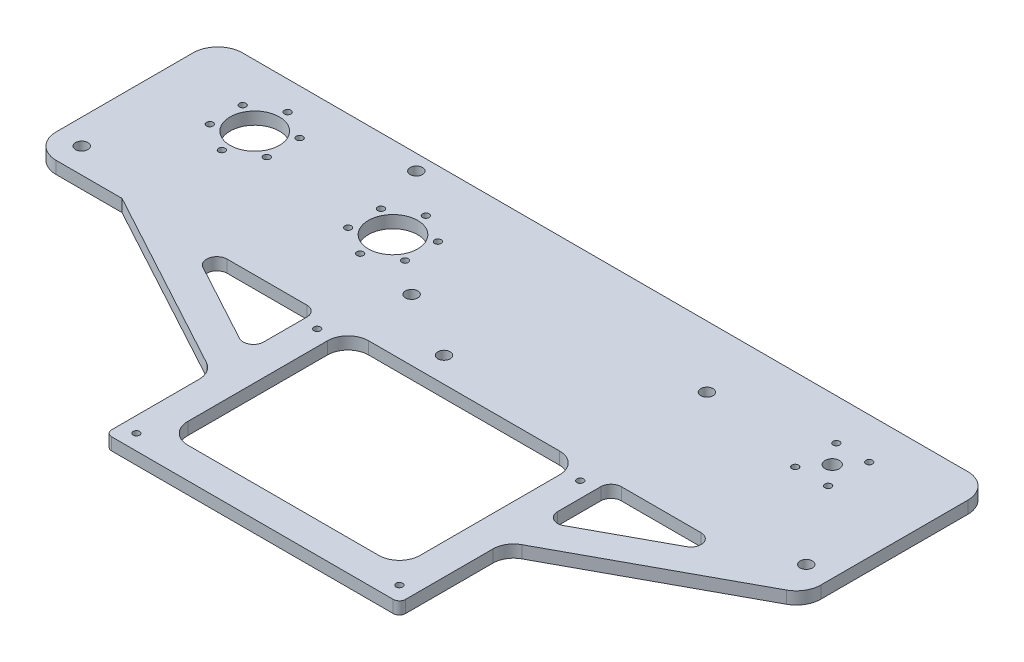
SolidWorks part; units mm, degrees
ref_plane "Plano frontal" through (0, 0, 0) normal (0, 0, 1) x (1, 0, 0)
ref_plane "Plano superior" through (0, 0, 0) normal (0, 1, 0) x (1, 0, 0)
ref_plane "Plano direito" through (0, 0, 0) normal (1, 0, 0) x (0, 0, -1)
sketch "Esboço1" plane through (0, 0, 0) normal (0, 1, 0) x (1, 0, 0)
  line L0 (98.5279, -50.6487) -> (137.3391, -50.6487)
  line L1 (139.722, -60.0443) -> (100.9108, -81.0841)
  line L2 (93.5279, -76.6884) -> (93.5279, -55.6487)
  line L3 (-46.4721, -153.6487) -> (90.5279, -153.6487)
  line L4 (93.5279, -150.6487) -> (93.5279, -108.1025)
  line L5 (98.7621, -99.3112) -> (182.2469, -54.0537)
  line L6 (188.5279, -43.5041) -> (188.5279, 28)
  line L7 (176.5279, 40) -> (-176.5279, 40)
  line L8 (-188.5279, 28) -> (-188.5279, -38.6487)
  line L9 (-176.5279, -50.6487) -> (-144.4721, -50.6487)
  line L10 (-144.4721, -50.6487) -> (-54.7063, -99.3112)
  line L11 (-49.4721, -108.1025) -> (-49.4721, -150.6487)
  line L12 (-93.2832, -50.6487) -> (-54.4721, -50.6487)
  line L13 (-49.4721, -55.6487) -> (-49.4721, -76.6884)
  line L14 (-56.855, -81.0841) -> (-95.6661, -60.0443)
  line L15 (78.5279, -60.6487) -> (78.5279, -128.6487)
  line L16 (68.5279, -138.6487) -> (-24.4721, -138.6487)
  line L17 (-34.4721, -128.6487) -> (-34.4721, -60.6487)
  line L18 (-24.4721, -50.6487) -> (68.5279, -50.6487)
  line L20 (132.5279, 0) -> (148.5279, 0) construction
  line L21 (132.5279, 0) -> (132.5279, 20) construction
  line L22 (132.5279, 20) -> (148.5279, 20) construction
  line L23 (148.5279, 0) -> (148.5279, 20) construction
  line L24 (132.5279, 0) -> (148.5279, 20) construction
  line L25 (132.5279, 20) -> (148.5279, 0) construction
  circle A0 centre (-41.9721, -58.1487) radius 1.6
  circle A1 centre (-41.9721, -146.1487) radius 1.6
  circle A2 centre (86.0279, -58.1487) radius 1.6
  circle A3 centre (86.0279, -146.1487) radius 1.6
  arc A4 (137.3391, -50.6487) -> (139.722, -60.0443) centre (137.3391, -55.6487) cw
  arc A5 (100.9108, -81.0841) -> (93.5279, -76.6884) centre (98.5279, -76.6884) cw
  arc A6 (93.5279, -55.6487) -> (98.5279, -50.6487) centre (98.5279, -55.6487) cw
  circle A8 centre (176.311, -38.4318) radius 3
  circle A9 centre (0, -38.4318) radius 3
  circle A11 centre (-140.5279, 10) radius 12
  circle A20 centre (-140.5279, 10) radius 16 construction
  circle A21 centre (-140.5279, -6) radius 1.6
  circle A22 centre (-154.3843, 2) radius 1.6
  circle A23 centre (-154.3843, 18) radius 1.6
  circle A24 centre (-84.3674, 32.5) radius 3
  circle A25 centre (-176.311, -38.4318) radius 3
  circle A26 centre (140.5279, 10) radius 3.5
  circle A27 centre (148.5279, 0) radius 1.6
  circle A28 centre (148.5279, 20) radius 1.6
  circle A29 centre (132.5279, 0) radius 1.6
  circle A30 centre (132.5279, 20) radius 1.6
  arc A31 (90.5279, -153.6487) -> (93.5279, -150.6487) centre (90.5279, -150.6487) ccw
  arc A32 (93.5279, -108.1025) -> (98.7621, -99.3112) centre (103.5279, -108.1025) cw
  arc A33 (182.2469, -54.0537) -> (188.5279, -43.5041) centre (176.5279, -43.5041) ccw
  arc A34 (188.5279, 28) -> (176.5279, 40) centre (176.5279, 28) ccw
  arc A35 (-176.5279, 40) -> (-188.5279, 28) centre (-176.5279, 28) ccw
  arc A36 (-188.5279, -38.6487) -> (-176.5279, -50.6487) centre (-176.5279, -38.6487) ccw
  arc A37 (-54.7063, -99.3112) -> (-49.4721, -108.1025) centre (-59.4721, -108.1025) cw
  arc A38 (-49.4721, -150.6487) -> (-46.4721, -153.6487) centre (-46.4721, -150.6487) ccw
  arc A39 (-54.4721, -50.6487) -> (-49.4721, -55.6487) centre (-54.4721, -55.6487) cw
  arc A40 (-49.4721, -76.6884) -> (-56.855, -81.0841) centre (-54.4721, -76.6884) cw
  arc A41 (-95.6661, -60.0443) -> (-93.2832, -50.6487) centre (-93.2832, -55.6487) cw
  arc A42 (78.5279, -128.6487) -> (68.5279, -138.6487) centre (68.5279, -128.6487) cw
  arc A43 (-24.4721, -138.6487) -> (-34.4721, -128.6487) centre (-24.4721, -128.6487) cw
  arc A44 (-34.4721, -60.6487) -> (-24.4721, -50.6487) centre (-24.4721, -60.6487) cw
  arc A45 (68.5279, -50.6487) -> (78.5279, -60.6487) centre (68.5279, -60.6487) cw
  circle A46 centre (-140.5279, 26) radius 1.6
  circle A47 centre (-126.6715, 18) radius 1.6
  circle A48 centre (-126.6715, 2) radius 1.6
  circle A49 centre (-63.2404, 0) radius 16 construction
  circle A50 centre (-63.2404, -16) radius 1.6
  circle A51 centre (-77.0968, -8) radius 1.6
  circle A52 centre (-77.0968, 8) radius 1.6
  circle A53 centre (-63.2404, 16) radius 1.6
  circle A54 centre (-49.384, 8) radius 1.6
  circle A55 centre (-49.384, -8) radius 1.6
  circle A56 centre (-63.2404, 0) radius 12
  circle A57 centre (-33.5279, -20.6487) radius 3
  circle A58 centre (79.5279, 10) radius 3
  point P43 (-140.5279, 10)
  point P116 (-63.2404, 0)
  point P123 (0, 40)
  dimension "D2" = 3
  dimension "D4" = 10
  dimension "D7" = 12
  dimension "D8" = 12
  dimension "D10" = 90.6487
  dimension "D11" = 61
  dimension "D12" = 77.2875
  dimension "D13" = 7.5
  dimension "D14" = 104.1605
  dimension "D16" = 12
  dimension "D20" = 10
  dimension "D21" = 3
  dimension "D22" = 48.4318
  dimension "D23" = 32
  dimension "D24" = 3.2
  dimension "D25" = 6
  dimension "D26" = 24
  dimension "D27" = 48
  dimension "D28" = 30
  dimension "D29" = 40
  dimension "D30" = 6
  dimension "D34" = 30
  dimension "D31" = 32
  dimension "D32" = 3.2
  dimension "D33" = 24
  dimension "D35" = 6
  dimension "D36" = 155
  dimension "D37" = 30
  dimension "D44" = 7
  dimension "D48" = 10
  dimension "D54" = 5
  dimension "D1" = 137
  dimension "D3" = 42.5462
  dimension "D5" = 94.9629
  dimension "D6" = 71.5041
  dimension "D9" = 377.0558
  dimension "D15" = 66.6487
  dimension "D17" = 32.0558
  dimension "D18" = 102.1075
  dimension "D19" = 42.5462
  dimension "D38" = 48
  dimension "D40" = 12.2169
  dimension "D41" = 12.2169
  dimension "D42" = 16
  dimension "D43" = 20
  dimension "D45" = 15
  dimension "D46" = 15
  dimension "D47" = 15
  dimension "D49" = 7.5
  dimension "D50" = 7.5
  dimension "D51" = 88
  dimension "D52" = 128
  dimension "D53" = 15
  dimension "D55" = 15
extrude "Ressalto-extrusão1" add sketch "Esboço1" against normal blind 6
